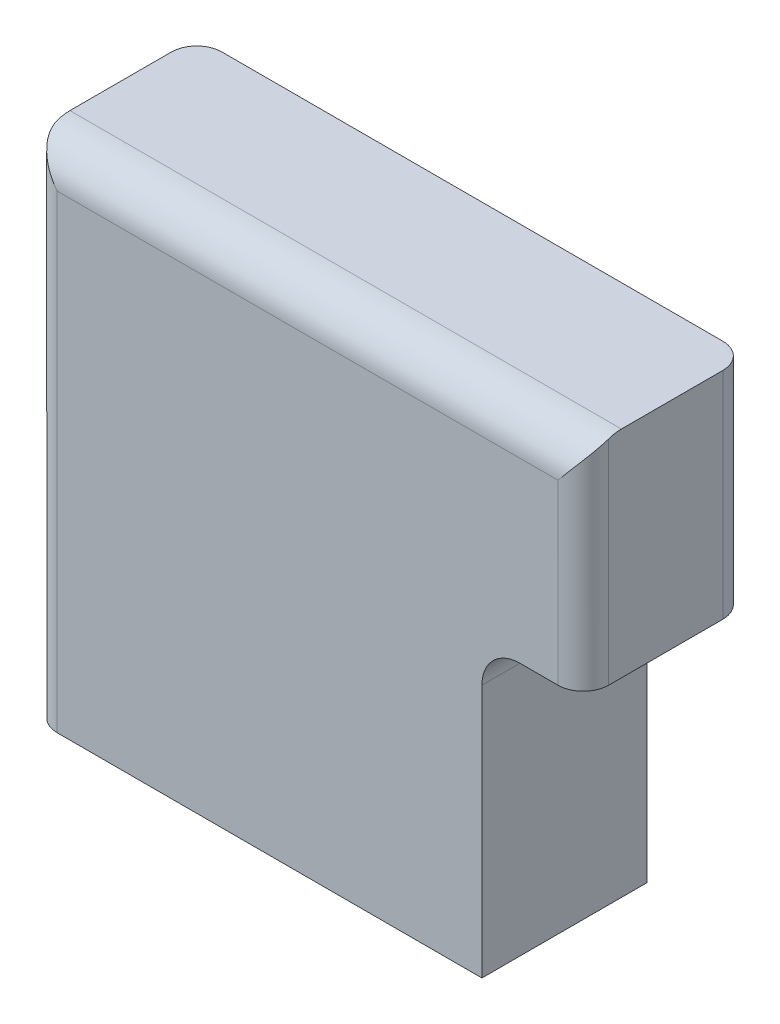
SolidWorks part; units mm, degrees
material "K110"
ref_plane "Front Plane" through (0, 0, 0) normal (0, 0, 1) x (1, 0, 0)
ref_plane "Top Plane" through (0, 0, 0) normal (0, 1, 0) x (1, 0, 0)
ref_plane "Right Plane" through (0, 0, 0) normal (1, 0, 0) x (0, 0, -1)
sketch "Sketch1" plane through (0, 0, 0) normal (0, 1, 0) x (1, 0, 0)
  line L1 (-21.75, -6.5) -> (21.75, -6.5)
  line L2 (-21.75, -6.5) -> (-21.75, 6.5)
  line L3 (-21.75, 6.5) -> (21.75, 6.5)
  line L4 (21.75, -6.5) -> (21.75, 6.5)
  line L5 (-21.75, -6.5) -> (21.75, 6.5) construction
  line L6 (-21.75, 6.5) -> (21.75, -6.5) construction
  point P0 (0, 0)
  dimension "D1" = 13
  dimension "D2" = 43.5
extrude "Boss-Extrude1" add sketch "Sketch1" against normal blind 40
fillet "Fillet1" radius 2 4 edges at (-21.75, -20, -6.5) (-21.75, -20, 6.5) (21.75, -20, -6.5) (21.75, -20, 6.5)
fillet "Fillet2" radius 3 1 edges at (0, 0, 6.5) tangent propagation no
ref_plane "Plane1" through (19.75, -40, 6.5) normal (1, 0, 0) x (0, 0, -1)
sketch "Sketch3" plane through (0, 0, 6.5) normal (0, 0, 1) x (1, 0, 0)
  line L0 (-19.75, -40) -> (19.75, -40) construction
  line L1 (13.75, -40) -> (21.75, -40)
  line L2 (13.75, -40) -> (13.75, -17)
  line L3 (13.75, -17) -> (21.75, -17)
  line L4 (21.75, -40) -> (21.75, -17)
  line L5 (21.75, -0.1716) -> (21.75, -40) construction
  dimension "D1" = 23
  dimension "D2" = 8
extrude "Cut-Extrude1" cut sketch "Sketch3" against normal through all
fillet "Fillet3" radius 3 1 edges at (13.75, -17, 0)
